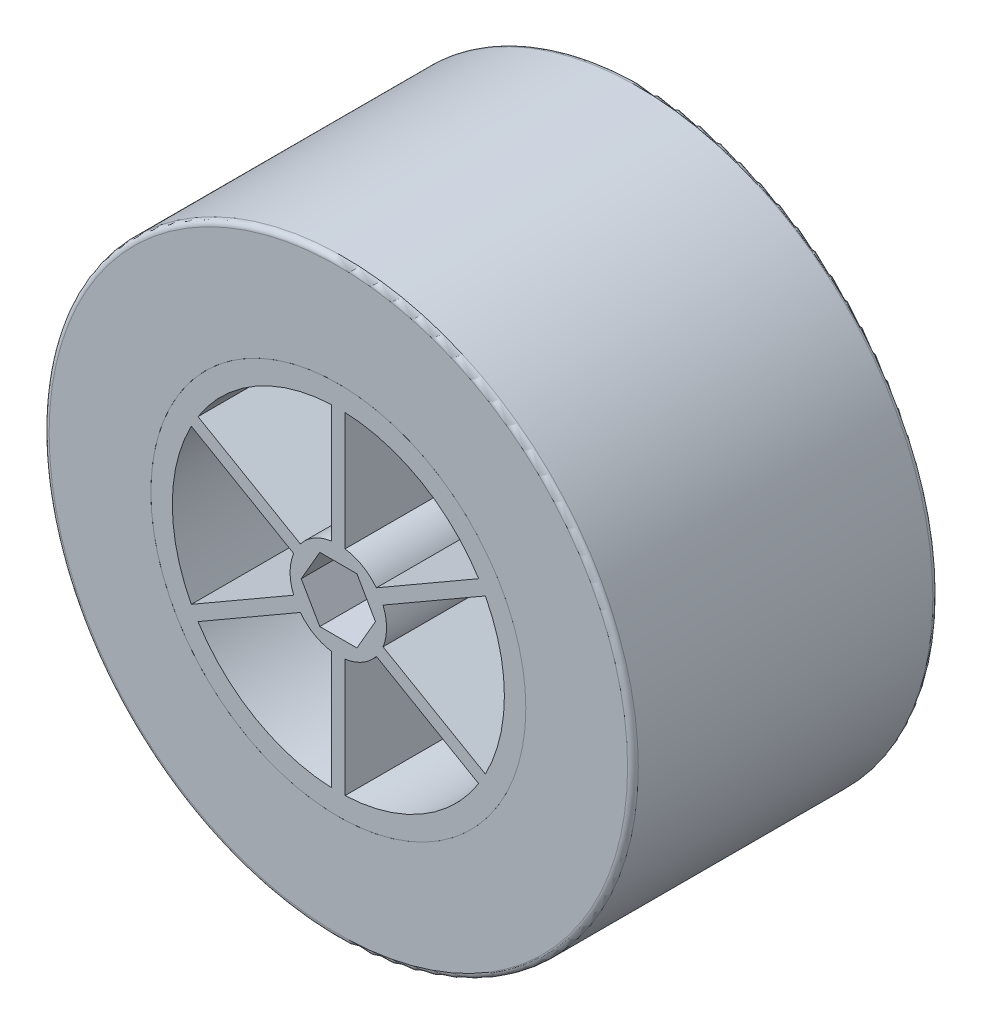
SolidWorks part; units mm, degrees
ref_plane "正面" through (0, 0, 0) normal (0, 0, 1) x (1, 0, 0)
ref_plane "平面" through (0, 0, 0) normal (0, 1, 0) x (1, 0, 0)
ref_plane "右側面" through (0, 0, 0) normal (1, 0, 0) x (0, 0, -1)
sketch "ｽｹｯﾁ1" plane through (0, 0, 0) normal (0, 0, 1) x (1, 0, 0)
  circle A0 centre (0, 0) radius 55
  circle A1 centre (0, 0) radius 35
  dimension "D1" = 110
  dimension "D2" = 70
extrude "ﾎﾞｽ - 押し出し1" add sketch "ｽｹｯﾁ1" along normal blind 28.5 and the other way blind 28.5
fillet "ﾌｨﾚｯﾄ1" radius 1 2 edges at (55, 0, -28.5) (55, 0, 28.5)
sketch "ｽｹｯﾁ2" plane through (0, 0, -28.5) normal (0, 0, -1) x (-1, 0, 0)
  circle A0 centre (0, 0) radius 35
  circle A1 centre (0, 0) radius 35 construction
  circle A2 centre (0, 0) radius 31
  dimension "D1" = 62
extrude "ﾎﾞｽ - 押し出し2" add sketch "ｽｹｯﾁ2" against normal up to surface (57 mm away) separate body up to face at (54, 0, 28.5)
sketch "ｽｹｯﾁ3" plane through (0, 0, -28.5) normal (0, 0, -1) x (-1, 0, 0)
  line L0 (31.35, 0) -> (-31.35, 0) construction
  line L1 (3.4641, 6) -> (-3.4641, 6)
  line L2 (-3.4641, 6) -> (-6.9282, 0)
  line L3 (-6.9282, 0) -> (-3.4641, -6)
  line L4 (-3.4641, -6) -> (3.4641, -6)
  line L5 (3.4641, -6) -> (6.9282, 0)
  line L6 (6.9282, 0) -> (3.4641, 6)
  line L7 (0, 9) -> (0, 31) construction
  line L8 (-1.25, 30.9748) -> (-1.25, 8.9128)
  line L9 (26.2, 16.5699) -> (7.0937, 5.5389)
  line L10 (7.7942, 4.5) -> (26.8468, 15.5) construction
  line L11 (27.45, -14.4049) -> (8.3437, -3.3739)
  line L12 (7.7942, -4.5) -> (26.8468, -15.5) construction
  line L13 (1.25, -30.9748) -> (1.25, -8.9128)
  line L14 (0, -9) -> (0, -31) construction
  line L15 (-26.2, -16.5699) -> (-7.0937, -5.5389)
  line L16 (-7.7942, -4.5) -> (-26.8468, -15.5) construction
  line L17 (-27.45, 14.4049) -> (-8.3437, 3.3739)
  line L18 (-7.7942, 4.5) -> (-26.8468, 15.5) construction
  line L19 (1.25, 30.9748) -> (1.25, 8.9128)
  line L20 (-26.2, 16.5699) -> (-7.0937, 5.5389)
  line L21 (-27.45, -14.4049) -> (-8.3437, -3.3739)
  line L22 (-1.25, -30.9748) -> (-1.25, -8.9128)
  line L23 (26.2, -16.5699) -> (7.0937, -5.5389)
  line L24 (27.45, 14.4049) -> (8.3437, 3.3739)
  arc A0 (-1.25, 8.9128) -> (-7.0937, 5.5389) centre (0, 0) ccw
  circle A1 centre (0, 0) radius 6 construction
  circle A2 centre (0, 0) radius 31 construction
  arc A3 (-8.3437, 3.3739) -> (-8.3437, -3.3739) centre (0, 0) ccw
  arc A4 (-7.0937, -5.5389) -> (-1.25, -8.9128) centre (0, 0) ccw
  arc A5 (1.25, -8.9128) -> (7.0937, -5.5389) centre (0, 0) ccw
  arc A6 (8.3437, -3.3739) -> (8.3437, 3.3739) centre (0, 0) ccw
  arc A7 (7.0937, 5.5389) -> (1.25, 8.9128) centre (0, 0) ccw
  point P1 (0, 0)
  point P19 (0, 0)
  point P20 (0, 0)
  point P40 (0, 0)
  circle M15 centre (0, 0) radius 31
  dimension "D1" = 12
  dimension "D2" = 18
  dimension "D3" = 2.5
  dimension "D4" = 6
extrude "ﾎﾞｽ - 押し出し3" add sketch "ｽｹｯﾁ3" against normal up to surface (57 mm away) contours L9 A7 L19 L8 A0 L20 L17 A3 L21 L15 A4 L22 L13 A5 L23 L11 A6 L24 L6 L5 L4 L3 L2 L1 M15 region at (0, 30.1719, -28.5) up to face at (35, 0, 28.5)
sketch "ｽｹｯﾁ4" plane through (0, 0, -28.5) normal (0, 0, -1) x (-1, 0, 0)
  line L0 (-3.4641, 6) -> (-6.9282, 0) construction
  line L1 (-6.9282, 0) -> (-3.4641, -6) construction
  line L2 (-3.4641, -6) -> (3.4641, -6) construction
  line L3 (3.4641, -6) -> (6.9282, 0) construction
  line L4 (6.9282, 0) -> (3.4641, 6) construction
  line L5 (3.4641, 6) -> (-3.4641, 6) construction
  line L6 (-3.4641, 6) -> (-6.9282, 0)
  line L7 (-6.9282, 0) -> (-3.4641, -6)
  line L8 (-3.4641, -6) -> (3.4641, -6)
  line L9 (3.4641, -6) -> (6.9282, 0)
  line L10 (6.9282, 0) -> (3.4641, 6)
  line L11 (3.4641, 6) -> (-3.4641, 6)
  line L12 (-1.3229, 1.5) -> (1.3229, 1.5)
  arc A0 (-1.3229, 1.5) -> (1.3229, 1.5) centre (0, 0) ccw
  dimension "D1" = 4
  dimension "D2" = 1.5
extrude "ﾎﾞｽ - 押し出し4" add sketch "ｽｹｯﾁ4" against normal blind 10 and the other way blind 2 separate body
sketch "ｽｹｯﾁ7" plane through (0, 0, -30.5) normal (0, 0, -1) x (-1, 0, 0)
  line L0 (1.3229, 1.5) -> (-1.3229, 1.5) construction
  line L1 (1.3229, 1.5) -> (-1.3229, 1.5)
  line L2 (-8, 6) -> (8, 6)
  line L3 (3.4641, 6) -> (-3.4641, 6) construction
  arc A0 (-8, 6) -> (8, 6) centre (0, 0) ccw
  arc A1 (-1.3229, 1.5) -> (1.3229, 1.5) centre (0, 0) ccw construction
  arc A2 (-1.3229, 1.5) -> (1.3229, 1.5) centre (0, 0) ccw
  dimension "D1" = 20
extrude "ﾎﾞｽ - 押し出し5" add sketch "ｽｹｯﾁ7" along normal blind 10
fillet "ﾌｨﾚｯﾄ2" radius 2 5 edges at (-5.1962, 3, -30.5) (-5.1962, -3, -30.5) (0, -6, -30.5) (5.1962, -3, -30.5) (5.1962, 3, -30.5)
fillet "ﾌｨﾚｯﾄ3" radius 2 2 edges at (-8, 6, -35.5) (8, 6, -35.5)
